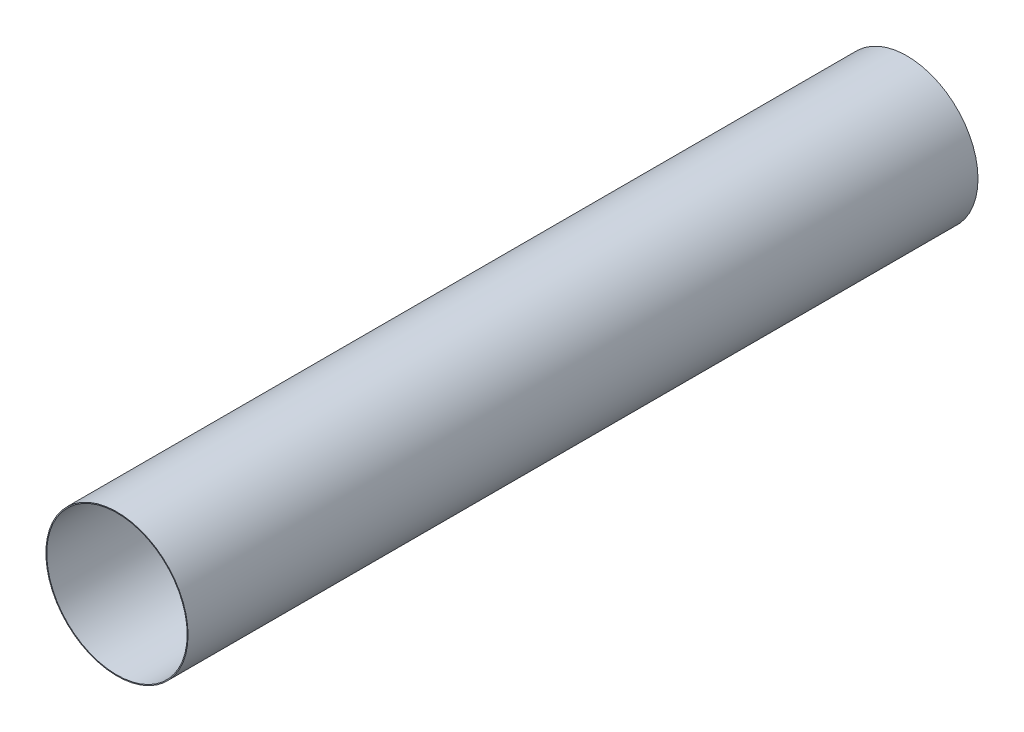
SolidWorks part; units mm, degrees
material "Thornel Mat VMA"
ref_plane "Front Plane" through (0, 0, 0) normal (0, 0, 1) x (1, 0, 0)
ref_plane "Top Plane" through (0, 0, 0) normal (0, 1, 0) x (1, 0, 0)
ref_plane "Right Plane" through (0, 0, 0) normal (1, 0, 0) x (0, 0, -1)
sketch "Sketch1" plane through (0, 0, 0) normal (0, 0, 1) x (1, 0, 0)
  circle A0 centre (0, 0) radius 81
  circle A1 centre (0, 0) radius 80
  dimension "D1" = 160
  dimension "D2" = 162
extrude "Boss-Extrude1" add sketch "Sketch1" along normal mid plane 900
